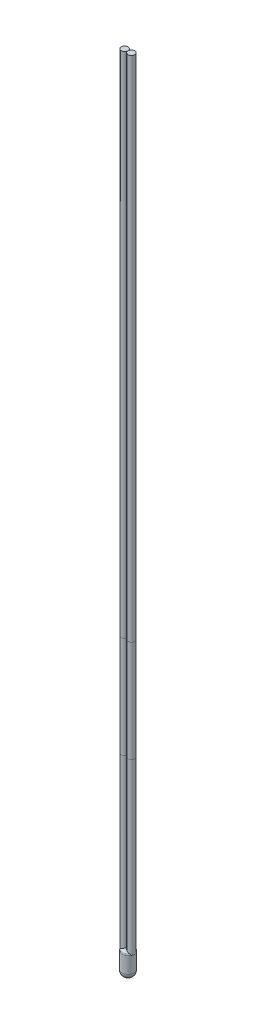
SolidWorks part; units mm, degrees
ref_plane "Alzado" through (0, 0, 0) normal (0, 0, 1) x (1, 0, 0)
ref_plane "Planta" through (0, 0, 0) normal (0, 1, 0) x (1, 0, 0)
ref_plane "Vista lateral" through (0, 0, 0) normal (1, 0, 0) x (0, 0, -1)
sketch "Croquis1" plane through (0, 0, 0) normal (0, 0, 1) x (1, 0, 0)
  line L0 (0, 0) -> (0, 2.5)
  line L1 (0.9, 2.8825) -> (0.9, -0.9)
  line L2 (0.9, 2.8825) -> (0.9, -0.9) construction
  arc A0 (0, 0) -> (0.9, -0.9) centre (0.9, 0) ccw
  arc A2 (0.9, 2.8825) -> (0, 2.5) centre (0.9, 1.6325) ccw
  dimension "D1" = 0.9
  dimension "D4" = 1.25
  dimension "D2" = 3.7825
  dimension "D3" = 1.6325
revolve "Revolución2" add sketch "Croquis1" angle 360 about L2
fillet "Redondeo1" radius 0.2 1 edges at (0, 2.5, 0)
ref_plane "Plano1" through (0, 2.4152, 0) normal (0, -1, 0) x (-1, 0, 0)
sketch "Croquis2" plane through (0, 2.4152, 0) normal (0, -1, 0) x (-1, 0, 0)
  line L0 (0, 0) -> (-2.221, 0) construction
  circle A1 centre (-1.41, 0) radius 0.5
  circle A2 centre (-0.4, 0) radius 0.5
  dimension "D3" = 1.01
  dimension "D1" = 1
  dimension "D2" = 0.4
extrude "Saliente-Extruir1" add sketch "Croquis2" against normal blind 25
sketch3d "Croquis3D3" [suppressed]
  spline S0 degree 3 poles (1.41, 2.4152, 0) (1.0603, 3.5631, 0.3272) (1.6484, 7.3886, 0.0467) (7.5523, 7.6503, -0.6505) (8.4693, 8.1567, 9.8569) (15.0427, 7.9249, 12.7408) (19.1583, 7.6729, 13.628) knots 0 0 0 0 0.164635 0.28119 0.551672 1 1 1 1
  spline S1 degree 3 poles (0.4, 2.4152, 0) (0.4448, 4.6268, 0.3906) (0.6458, 7.7943, -0.1737) (6.3043, 8.4584, -0.8157) (9.3949, 8.4545, 3.1205) (6.9679, 9.5284, 10.8325) (19.295, 8.8861, 13.6236) knots 0 0 0 0 0.158889 0.351328 0.437845 1 1 1 1
sketch "Croquis3" [suppressed] plane through (0, 2.4152, 0) normal (0, -1, 0) x (-1, 0, 0)
  line L0 (-0.9, 0.8333) -> (-0.9, -0.8333) construction
  line L1 (-0.0667, 0) -> (-1.7333, 0) construction
  circle A0 centre (-1.37, 0) radius 0.45
  circle A1 centre (-0.43, 0) radius 0.45
  circle A2 centre (-0.9, 0) radius 0.8333 construction
  dimension "D2" = 0.9
  dimension "D1" = 0.47
ref_plane "Plano2" [suppressed] through (0.43, 0, 0) normal (1, 0, 0) x (0, 0, -1)
sketch "Croquis5" [suppressed] plane through (0.43, 0, 0) normal (1, 0, 0) x (0, 0, -1)
  line L0 (0, 2.4152) -> (0, 3.5168)
sketch "Croquis6" [suppressed] plane through (0, 0, 0) normal (0, 0, 1) x (1, 0, 0)
  line L0 (0.43, 3.5168) -> (8.4601, 14.9849)
  line L1 (0.43, 3.5168) -> (6.2015, 3.5168) construction
  line L2 (8.4601, 14.9849) -> (14.7151, 6.6842) construction
  dimension "D1" = 14
  dimension "D2" = 55
  dimension "D3" = 72
ref_plane "Plano3" [suppressed] through (12.2183, 9.2072, -2.6976) normal (0.7865, 0.5927, -0.1736) x (0.2514, -0.5641, -0.7865)
sketch "Croquis7" [suppressed] plane through (12.2183, 9.2072, -2.6976) normal (0.7865, 0.5927, -0.1736) x (0.2514, -0.5641, -0.7865)
  line L0 (-6.3258, 3.843) -> (-24.1613, -12.2162)
  line L1 (-6.3258, 3.843) -> (-6.3258, 15.4439) construction
  dimension "D1" = 132
  dimension "D2" = 24
ref_plane "Plano4" [suppressed] through (-4.1263, 5.5348, 0.607) normal (0.5954, -0.7986, -0.0876) x (-0.8025, -0.5964, -0.0175)
sketch "Croquis8" [suppressed] plane through (-4.1263, 5.5348, 0.607) normal (0.5954, -0.7986, -0.0876) x (-0.8025, -0.5964, -0.0175)
  line L0 (-20.3032, -22.6735) -> (-23.3032, -22.6735)
  line L1 (-23.3032, -22.6735) -> (-28.501, -47.1272)
  line L2 (-28.501, -47.1272) -> (-62.604, -39.2539)
  line L3 (-62.604, -39.2539) -> (-57.0398, -16.9371)
  dimension "D1" = 102
  dimension "D2" = 3
  dimension "D3" = 25
  dimension "D4" = 89
  dimension "D5" = 89
  dimension "D6" = 23
  dimension "D7" = 35
ref_plane "Plano5" [suppressed] through (42.2967, 38.1848, 18.4753) normal (-0.2313, -0.066, -0.9707) x (-0.9728, 0.0053, 0.2314)
sketch "Croquis9" [suppressed] plane through (42.2967, 38.1848, 18.4753) normal (-0.2313, -0.066, -0.9707) x (-0.9728, 0.0053, 0.2314)
  line L0 (0, 0) -> (-2.2943, -3.2766)
  line L1 (0, 0) -> (0, 5.9543) construction
  line L2 (0, 0) -> (7.2144, 0) construction
  dimension "D1" = 145
  dimension "D2" = 4
sketch3d "Croquis3D4" [suppressed]
  line L0 (0.43, 2.4152, 0) -> (0.43, 3.5168, 0) construction
  line L1 (0.43, 3.5168, 0) -> (8.4601, 14.9849, 0) construction
  line L2 (8.4601, 14.9849, 0) -> (13.0346, 15.8129, 23.5454) construction
  line L3 (13.0346, 15.8129, 23.5454) -> (15.4421, 17.602, 23.598) construction
  line L4 (15.4421, 17.602, 23.598) -> (20.5489, 18.728, 48.0449) construction
  line L5 (20.5489, 18.728, 48.0449) -> (47.6158, 39.7017, 40.8003) construction
  line L6 (47.6158, 39.7017, 40.8003) -> (42.2967, 38.1848, 18.4753) construction
  line L7 (0.43, 2.4152, 0) -> (0.43, 2.8862, 0)
  line L8 (0.7917, 4.0333, 0) -> (4.4648, 9.2791, 0)
  line L9 (9.7877, 15.2252, 6.8336) -> (12.7989, 15.7703, 22.3322)
  line L10 (14.027, 16.5504, 23.5671) -> (14.4673, 16.8776, 23.5767)
  line L11 (15.6903, 17.6567, 24.7858) -> (19.3017, 18.453, 42.0744)
  line L12 (25.2706, 22.3868, 46.7811) -> (41.3201, 34.8233, 42.4854)
  line L13 (45.7331, 39.1648, 32.8984) -> (42.7593, 38.3167, 20.4166)
  line L14 (42.2967, 38.1848, 18.4753) -> (44.562, 34.9033, 18.1586) construction
  line L15 (43.4294, 36.544, 18.3169) -> (44.562, 34.9033, 18.1586)
  arc A0 (41.3201, 34.8233, 42.4854) -> (45.7331, 39.1648, 32.8984) centre (39.5777, 34.3793, 34.6901) ccw
  arc A1 (4.4648, 9.2791, 0) -> (9.7877, 15.2252, 6.8336) centre (5.3669, 8.6474, 7.9238) ccw
  arc A2 (19.3017, 18.453, 42.0744) -> (25.2706, 22.3868, 46.7811) centre (23.9638, 22.0537, 40.9347) ccw
  arc A3 (14.4673, 16.8776, 23.5767) -> (15.6903, 17.6567, 24.7858) centre (14.5247, 16.7566, 25.0707) ccw
  arc A4 (12.7989, 15.7703, 22.3322) -> (14.027, 16.5504, 23.5671) centre (13.9696, 16.6715, 22.0731) ccw
  arc A5 (42.7593, 38.3167, 20.4166) -> (43.4294, 36.544, 18.3169) centre (43.8919, 36.6759, 20.2582) ccw
  arc A6 (0.43, 2.8862, 0) -> (0.7917, 4.0333, 0) centre (2.43, 2.8862, 0) ccw
  point P11 (47.6158, 39.7017, 40.8003)
  point P13 (34.8145, 40.7684, 35.3908)
  point P16 (8.4601, 14.9849, 0)
  point P18 (11.8577, 4.1025, 6.8226)
  point P21 (20.5489, 18.728, 48.0449)
  point P23 (20.3914, 26.8456, 41.4602)
  point P26 (15.4421, 17.602, 23.598)
  point P28 (15.4178, 15.5586, 24.9393)
  point P31 (13.0346, 15.8129, 23.5454)
  point P33 (13.0765, 17.8694, 22.2045)
  point P36 (42.2967, 38.1848, 18.4753)
  point P38 (42.3098, 35.5399, 20.7124)
  point P41 (0.43, 3.5168, 0)
  point P43 (2.43, 2.8862, -2)
  dimension "D1" = 8
  dimension "D2" = 6
  dimension "D3" = 1.5
  dimension "D4" = 2
  dimension "D5" = 2
sweep "Barrer1" [suppressed] add profiles "Croquis3" path "Croquis3D4"
extrude "Saliente-Extruir6" add sketch "Croquis2<3>" against normal blind 15 from offset 25 separate body offset against normal yes
sketch "Croquis2<3>" plane through (0, 2.4152, 0) normal (0, -1, 0) x (-1, 0, 0) same geometry as "Croquis2"
extrude "Saliente-Extruir7" add sketch "Croquis2<4>" against normal blind 75 from offset 40 separate body offset against normal yes
sketch "Croquis2<4>" plane through (0, 2.4152, 0) normal (0, -1, 0) x (-1, 0, 0) same geometry as "Croquis2"
